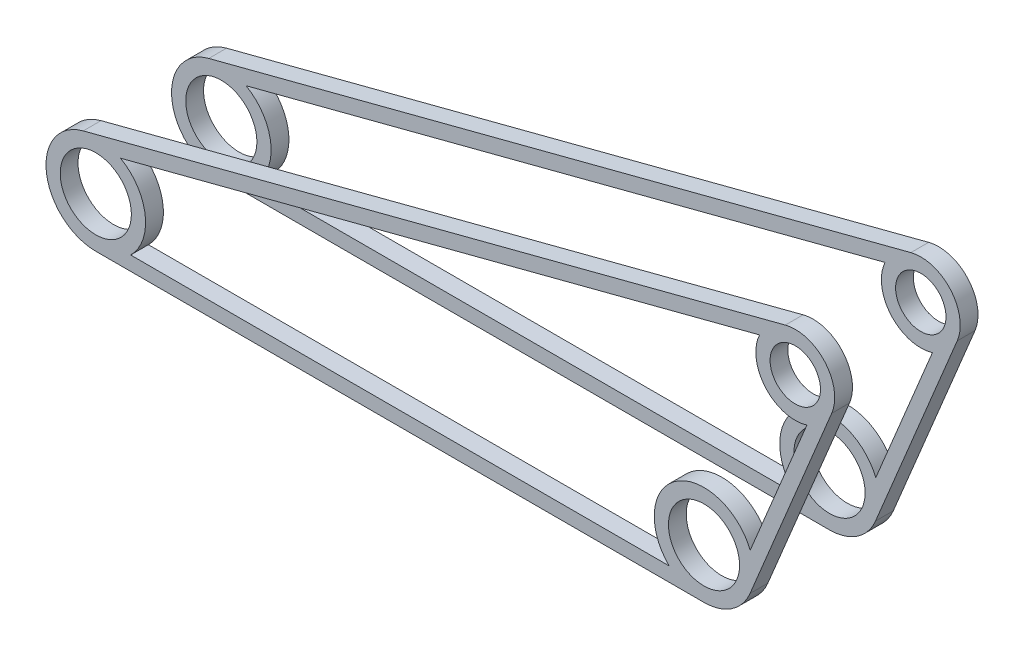
SolidWorks part; units mm, degrees
material "AISI 4130 Steel, annealed at 865C"
ref_plane "Front Plane" through (0, 0, 0) normal (0, 0, 1) x (1, 0, 0)
ref_plane "Top Plane" through (0, 0, 0) normal (0, 1, 0) x (1, 0, 0)
ref_plane "Right Plane" through (0, 0, 0) normal (1, 0, 0) x (0, 0, -1)
sketch "Sketch1" plane through (0, 0, 0) normal (0, 0, 1) x (1, 0, 0)
  line L0 (0, 0) -> (108.585, 0) construction
  line L1 (108.585, 0) -> (124.8778, 34.4406) construction
  line L2 (124.8778, 34.4406) -> (0, 0) construction
  line L3 (-2.2409, 8.6029) -> (123.1032, 41.2533)
  line L4 (131.3803, 31.7426) -> (116.7963, -3.407)
  line L5 (108.585, -8.89) -> (0, -8.89)
  line L6 (-1.6007, 6.1449) -> (123.7434, 38.7953)
  line L7 (0, -6.35) -> (108.585, -6.35)
  line L8 (114.4502, -2.4335) -> (129.0342, 32.7161)
  line L9 (111.596, -21.6868) -> (108.585, 0) construction
  circle A0 centre (0, 0) radius 6.35
  circle A1 centre (108.585, 0) radius 6.35
  circle A2 centre (124.8778, 34.4406) radius 4.5
  circle A3 centre (0, 0) radius 8.89
  circle A4 centre (108.585, 0) radius 8.89
  circle A5 centre (124.8778, 34.4406) radius 7.04
  dimension "D1" = 9
  dimension "D2" = 12.7
  dimension "D3" = 12.7
  dimension "D6" = 2.54
  dimension "D7" = 2.54
  dimension "D8" = 2.54
  dimension "D4" = 108.585
  dimension "D5" = 129.54
  dimension "D9" = 38.1
extrude "Boss-Extrude1" add sketch "Sketch1" along normal blind 3.175 from offset 9.6177 contours A5 L3 A3 L6 | L6 A3 L7 A0 | A4 L7 A3 L5 | L7 A4 L8 A1 | A5 L8 A4 L4 | A5 L6 A2 L8 | L7 A3 L6 A0 | L8 A4 L7 A1 | L6 A5 L8 A2 region at (1.146, 8.5805, 0) region at (60.9965, 23.7793, 0) region at (129.0654, 39.8588, 0) region at (54.2925, -7.6406, 0) region at (7.54, 4.3695, 0) region at (121.1641, 37.9583, 0) region at (105.2983, -8.0507, 0) region at (123.0705, 14.8619, 0) region at (103.7755, 7.2025, 0)
extrude "Boss-Extrude2" add sketch "Sketch1<4>" against normal blind 3.175 from offset 9.6177 separate body contours A5 L3 A3 L6 | L6 A3 L7 A0 | L7 A3 L6 A0 | A4 L7 A3 L5 | L7 A4 L8 A1 | L8 A4 L7 A1 | A5 L8 A4 L4 | L6 A5 L8 A2 | A5 L6 A2 L8 region at (1.146, 8.5805, 0) region at (60.9965, 23.7793, 0) region at (129.0654, 39.8588, 0) region at (54.2925, -7.6406, 0) region at (7.54, 4.3695, 0) region at (121.1641, 37.9583, 0) region at (105.2983, -8.0507, 0) region at (123.0705, 14.8619, 0) region at (103.7755, 7.2025, 0) offset against normal yes
sketch "Sketch1<4>" plane through (0, 0, 0) normal (0, 0, 1) x (1, 0, 0) same geometry as "Sketch1"
equation "\"D19@Boss-Extrude2\"=\"Gap\"/2"
equation "\"Gap\"= .8198 - 1 / 16"
equation "\"D19@Boss-Extrude1\"=\"Gap\"/2"
